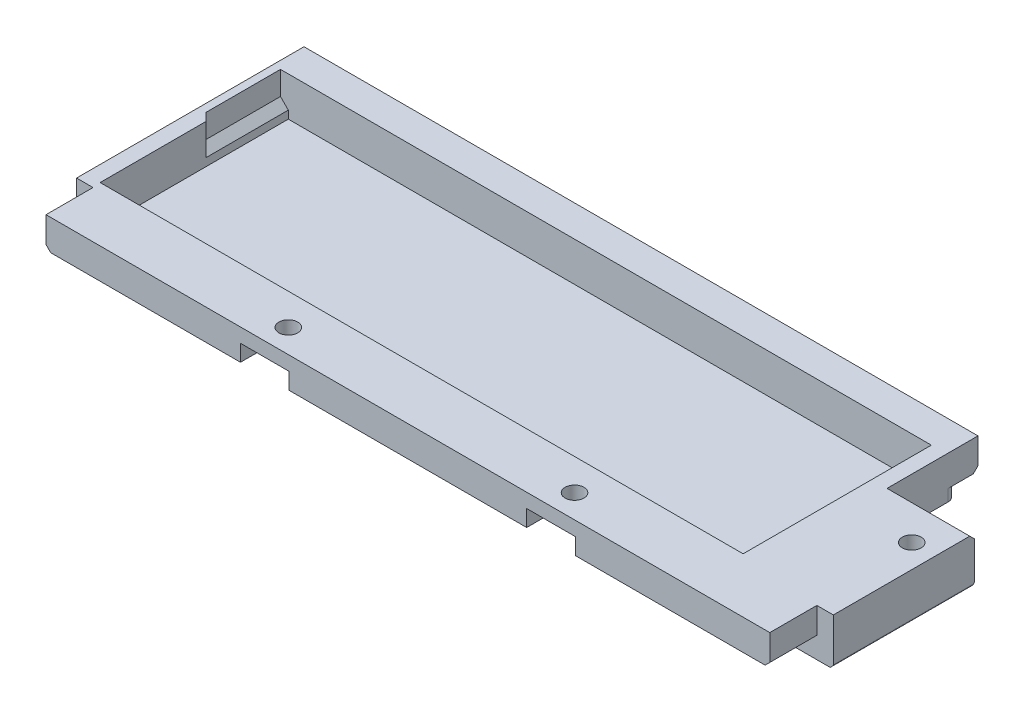
SolidWorks part; units mm, degrees
ref_plane "前视基准面" through (0, 0, 0) normal (0, 0, 1) x (1, 0, 0)
ref_plane "上视基准面" through (0, 0, 0) normal (0, 1, 0) x (1, 0, 0)
ref_plane "右视基准面" through (0, 0, 0) normal (1, 0, 0) x (0, 0, -1)
sketch "草图1" plane through (0, 0, 0) normal (0, 1, 0) x (1, 0, 0)
  line L1 (0, 0) -> (96.5, 0)
  line L2 (0, 0) -> (0, 35)
  line L3 (0, 35) -> (96.5, 35)
  line L4 (96.5, 0) -> (96.5, 35)
  dimension "D1" = 35
  dimension "D2" = 96.5
extrude "凸台-拉伸1" add sketch "草图1" along normal blind 6
sketch "草图2" plane through (0, 6, 0) normal (0, 1, 0) x (1, 0, 0)
  line L0 (96.5, 35) -> (0, 35) construction
  line L1 (2, 7) -> (84, 7)
  line L2 (2, 7) -> (2, 31)
  line L3 (2, 31) -> (84, 31)
  line L4 (84, 7) -> (84, 31)
  line L5 (0, 35) -> (0, 0) construction
  dimension "D1" = 24
  dimension "D2" = 82
  dimension "D3" = 4
  dimension "D4" = 2
extrude "切除-拉伸1" cut sketch "草图2" against normal blind 5
sketch "草图3" plane through (0, 0, 0) normal (0, 0, 1) x (1, 0, 0)
  line L0 (96.5, 6) -> (96.5, 0) construction
  line L1 (0, 0) -> (96.5, 0) construction
  line L2 (0, 6) -> (0, 0) construction
  line L3 (96.5, 6) -> (96.5, 0)
  line L4 (0, 0) -> (96.5, 0)
  line L5 (0, 6) -> (0, 0)
  line L6 (94.4, 6) -> (94.4, 2.1)
  line L7 (2.1, 2.1) -> (94.4, 2.1)
  line L8 (2.1, 6) -> (2.1, 2.1)
  line L9 (0, 6) -> (2.1, 6)
  line L10 (94.4, 6) -> (96.5, 6)
  dimension "D1" = 2.1
extrude "切除-拉伸2" cut sketch "草图3" against normal blind 6
sketch "草图4" plane through (0, 0, 0) normal (0, -1, 0) x (1, 0, 0)
  line L0 (0, -32.1989) -> (86, -32.1989) construction
  line L1 (86, -32.1989) -> (86, -24.9989) construction
  line L2 (87, -23.9989) -> (96.5, -23.9989) construction
  line L3 (0, -32.1989) -> (85.95, -32.1989)
  line L4 (86, -32.1989) -> (86, -23.9989) construction
  line L5 (86, -23.9989) -> (96.5, -23.9989)
  line L6 (86, -23.9989) -> (85.95, -23.9989)
  line L7 (85.95, -23.9989) -> (85.95, -32.1989)
  line L10 (96.5, -6) -> (0, -6)
  line L11 (0, -6) -> (0, -35)
  line L12 (0, -35) -> (96.5, -35)
  line L13 (96.5, -35) -> (96.5, -6)
  line L15 (0, -32.1989) -> (0, -35)
  line L16 (0, -35) -> (96.5, -35)
  line L17 (96.5, -35) -> (96.5, -23.9989)
  dimension "D2" = 0.1
  dimension "D1" = 0
extrude "切除-拉伸3" cut sketch "草图4" against normal blind 2.1
fillet "圆角1" radius 1 1 edges at (85.95, 1.05, -32.1989)
chamfer "倒角1" distance 0.6 angle 45 4 edges at (42.475, 0, -32.1989) (85.6571, 0, -31.9061) (85.95, 0, -27.5989) (91.225, 0, -23.9989)
chamfer "倒角2" distance 0.4 angle 45 2 edges at (0, 0, -18.7995) (96.5, 0, -14.6995)
fillet "圆角2" radius 0.2 4 edges at (0, 0.4, -18.9995) (0.4, 0, -18.7995) (96.1, 0, -14.6995) (96.5, 0.4, -14.8995)
sketch "草图5" plane through (0, 2.1, 0) normal (0, -1, 0) x (1, 0, 0)
  line L0 (85.95, -23.9989) -> (85.95, -31.1989) construction
  line L1 (96.5, -35) -> (85.95, -35)
  line L2 (96.5, -35) -> (96.5, -23.9989)
  line L3 (96.5, -23.9989) -> (85.95, -23.9989)
  line L4 (85.95, -35) -> (85.95, -23.9989)
  line L5 (96.5, -23.9989) -> (85.95, -23.9989) construction
extrude "切除-拉伸5" cut sketch "草图5" against normal through all
chamfer "倒角3" distance 0.6 angle 45 3 edges at (2.1, 2.1, -3) (94.4, 2.1, -3) (91.225, 6, -23.9989)
chamfer "倒角4" distance 0.6 angle 45 1 edges at (42.975, 2.1, -35)
sketch "草图6" plane through (0, 6, 0) normal (0, 1, 0) x (1, 0, 0)
  line L1 (2, 31) -> (1, 31)
  line L2 (2, 31) -> (2, 21.5)
  line L3 (2, 21.5) -> (1, 21.5)
  line L4 (1, 31) -> (1, 21.5)
  dimension "D1" = 9.5
  dimension "D2" = 1
extrude "切除-拉伸6" cut sketch "草图6" against normal blind 3
chamfer "倒角5" distance 1 angle 45 1 edges at (2, 3, -26.25)
chamfer "倒角6" distance 1 angle 45 1 edges at (2, 4, -21.5)
sketch "草图7" plane through (0, 0, 0) normal (0, 0, 1) x (1, 0, 0)
  line L0 (69.5, 2) -> (69.5, 4) construction
  line L1 (63.5, 4) -> (63.5, 2) construction
  line L2 (33, 2) -> (33, 4) construction
  line L3 (27, 4) -> (27, 2) construction
  line L4 (69.5, 2) -> (69.5, 4) construction
  line L5 (63.5, 4) -> (63.5, 2) construction
  line L6 (33, 2) -> (33, 4) construction
  line L7 (27, 4) -> (27, 2) construction
  line L8 (27, 4) -> (33, 4) construction
  line L9 (63.5, 4) -> (69.5, 4) construction
  line L10 (93.8, 2.1) -> (2.7, 2.1) construction
  line L11 (69.6, 2.1) -> (63.4, 2.1)
  line L12 (26.9, 2.1) -> (26.9, 4.2)
  line L13 (26.9, 4.2) -> (33.1, 4.2)
  line L14 (33.1, 4.2) -> (33.1, 2.1)
  line L15 (63.4, 2.1) -> (63.4, 4.2)
  line L16 (63.4, 4.2) -> (69.6, 4.2)
  line L17 (69.6, 4.2) -> (69.6, 2.1)
  line L18 (33.1, 2.1) -> (26.9, 2.1)
  dimension "D1" = 0.1
  dimension "D2" = 0.1
  dimension "D3" = 0.2
  dimension "D4" = 0.1
extrude "切除-拉伸7" cut sketch "草图7" against normal blind 6
sketch "草图8" plane through (0, 4.2, 0) normal (0, -1, 0) x (1, 0, 0)
  circle A0 centre (66.5, -2.9989) radius 1.2 construction
  circle A1 centre (30, -2.9989) radius 1.2 construction
  circle A2 centre (66.5, -2.9989) radius 1.2
  circle A3 centre (30, -2.9989) radius 1.2
extrude "切除-拉伸8" cut sketch "草图8" against normal through all
ref_plane "基准面1" through (73.649, 7.36, -22.4989) normal (0, 0, -1) x (-1, 0, 0)
ref_plane "基准面2" through (59.6, 9.54, -28.5989) normal (0, 0, 1) x (1, 0, 0)
sketch "草图11" plane through (0, 0, 0) normal (0, -1, 0) x (1, 0, 0)
  circle A0 centre (93.5, -18.9989) radius 1.5 construction
  circle A1 centre (93.5, -18.9989) radius 1.5 construction
  circle A2 centre (93.5, -18.9989) radius 1.2
  circle A3 centre (93.5, -18.9989) radius 2.05
  dimension "D1" = 2.4
  dimension "D2" = 4.1
extrude "切除-拉伸9" cut sketch "草图11" against normal through all contours A2
extrude "切除-拉伸10" cut sketch "草图11<3>" against normal blind 2 contours A3
sketch "草图11<3>" plane through (0, 0, 0) normal (0, -1, 0) x (1, 0, 0) same geometry as "草图11"
